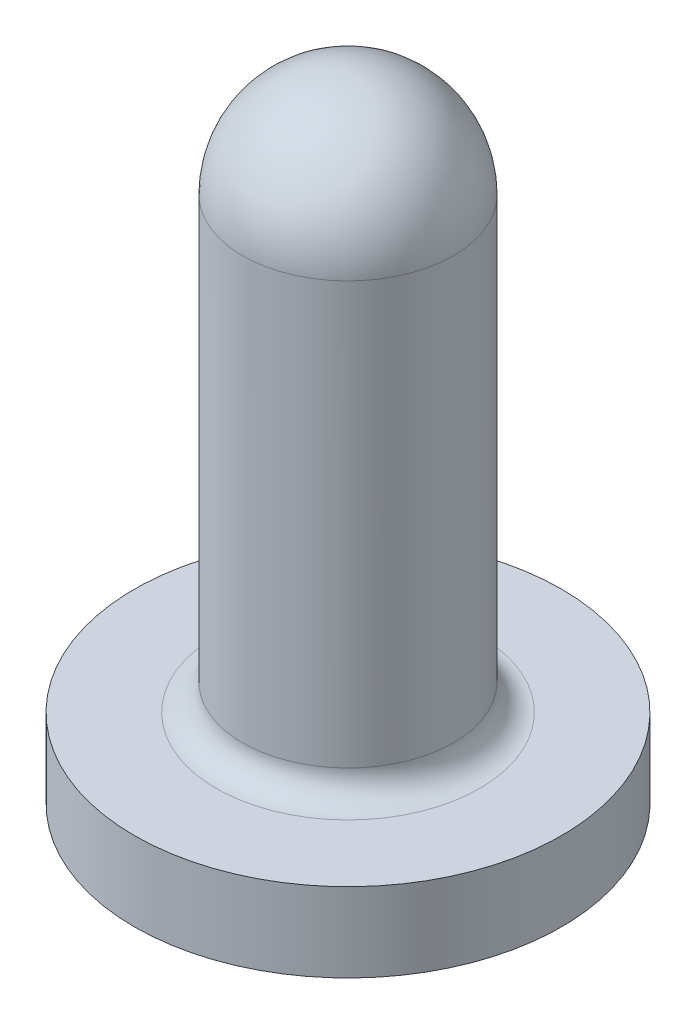
SolidWorks part; units mm, degrees
ref_plane "Front Plane" through (0, 0, 0) normal (0, 0, 1) x (1, 0, 0)
ref_plane "Top Plane" through (0, 0, 0) normal (0, 1, 0) x (1, 0, 0)
ref_plane "Right Plane" through (0, 0, 0) normal (1, 0, 0) x (0, 0, -1)
sketch "Sketch1" plane through (0, 0, 0) normal (0, 1, 0) x (1, 0, 0)
  circle A0 centre (0, 0) radius 2
  dimension "D1" = 4
extrude "Boss-Extrude1" add sketch "Sketch1" along normal blind 12
sketch "Sketch6" plane through (0, 0, 0) normal (0, -1, 0) x (1, 0, 0)
  circle A0 centre (0, 0) radius 4.05
  dimension "D1" = 8.1
extrude "Boss-Extrude3" add sketch "Sketch6" against normal blind 1.5
sketch "Sketch2" plane through (0, 0, 0) normal (0, -1, 0) x (1, 0, 0)
  circle A0 centre (0, 0) radius 1
  dimension "D1" = 2
extrude "Cut-Extrude1" cut sketch "Sketch2" against normal blind 10
draft "Draft1" type of draft neutral plane draft angle 1 faces to draft 1 face at (0, 10, -1) neutral plane through (0, 10, 0) neutral plane normal (0, -1, 0) parameters "D1"=1
sketch "Sketch7" plane through (0, 0, 0) normal (0, 0, 1) x (1, 0, 0)
  line L0 (2, 1.5) -> (2, 12) construction
  line L1 (2, 12) -> (-2, 12) construction
  line L4 (0, 10) -> (0, 12) construction
  line L5 (2, 10) -> (3.0807, 10)
  line L6 (3.0807, 10) -> (3.0807, 13.0807)
  line L7 (3.0807, 13.0807) -> (0, 13.0807)
  line L8 (0, 13.0807) -> (0, 12)
  arc A0 (2, 10) -> (0, 12) centre (0, 10) ccw
  point P5 (3.8101, 10.5)
  point P11 (4.5807, 14.2583)
  dimension "D1" = 3.0807
revolve "Cut-Revolve3" cut sketch "Sketch7" angle 360 about L4
sketch "Sketch3" plane through (0, 10, 0) normal (0, -1, 0) x (1, 0, 0)
  line L0 (1.151, 0.2338) -> (0.746, 0)
  line L1 (0.746, 0) -> (1.151, -0.2338)
  line L2 (0, 0) -> (1.1746, 0) construction
  line L3 (1.151, 0.2338) -> (1.151, -0.2338) construction
  line L6 (-0.373, -1.1138) -> (-0.373, -0.6461)
  line L7 (-0.373, -0.6461) -> (-0.778, -0.8799)
  line L10 (-0.373, -1.1138) -> (-0.778, -0.8799) construction
  line L11 (-0.778, 0.8799) -> (-0.373, 0.6461)
  line L14 (-0.373, 0.6461) -> (-0.373, 1.1138)
  line L15 (-0.778, 0.8799) -> (-0.373, 1.1138) construction
  arc A1 (-0.778, -0.8799) -> (-0.373, -1.1138) centre (0, 0) ccw
  arc A2 (-0.373, 1.1138) -> (-0.778, 0.8799) centre (0, 0) ccw
  circle A7 centre (0, 0) radius 1.1746 construction
  arc A8 (1.151, -0.2338) -> (1.151, 0.2338) centre (0, 0) ccw
  circle A9 centre (0, 0) radius 1 construction
  point P16 (0, 0)
  dimension "D1" = 0.254
extrude "Boss-Extrude2" add sketch "Sketch3" along normal up to surface (10 mm away) up to face at (0, 0, 1.1746)
sketch "ref_for_revolve" plane through (0, 0, 0) normal (0, -1, 0) x (1, 0, 0)
  circle A0 centre (0, 0) radius 1.1746 construction
sketch "Sketch4" plane through (0, 0, 0) normal (0, 0, 1) x (1, 0, 0)
  line L1 (1.1746, 0) -> (0.746, 0.4286)
  line L2 (0.746, 0.4286) -> (0, 0.4286)
  line L4 (0, 0.4286) -> (0, 0)
  line L5 (0.746, 0.4286) -> (0.746, 0) construction
  line L6 (0.746, 0) -> (1.1746, 0) construction
  line L7 (1.1746, 0) -> (0, 0)
  line L8 (-0.373, 0) -> (1.151, 0) construction
  line L9 (-1.1746, 0) -> (1.1746, 0) construction
  point P7 (0, 0)
  point P8 (1.2819, 0)
  point P12 (0, 0)
  point P13 (1.368, 0)
  point P14 (1.1559, 0)
  point P17 (0, 0)
revolve "Cut-Revolve1" cut sketch "Sketch4" angle 360 about L4
fillet "Fillet1" radius 0.5 1 edges at (0, 1.5, -2)
